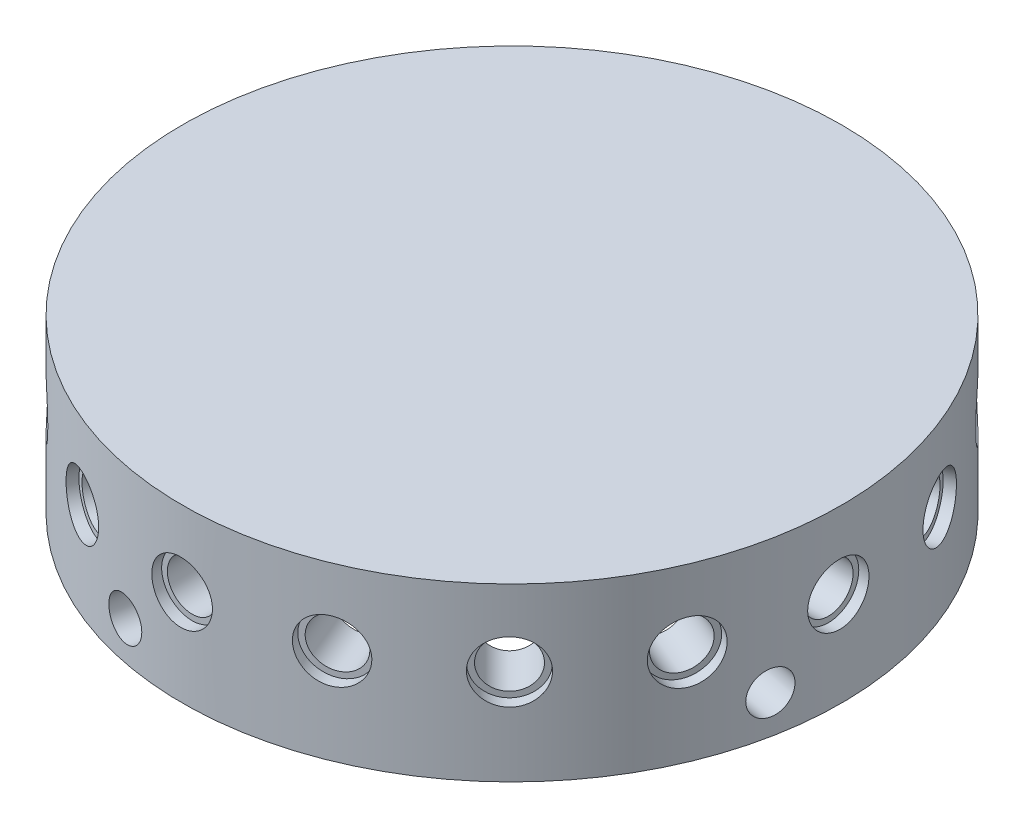
SolidWorks part; units mm, degrees
ref_plane "Płaszczyzna przednia" through (0, 0, 0) normal (0, 0, 1) x (1, 0, 0)
ref_plane "Płaszczyzna górna" through (0, 0, 0) normal (0, 1, 0) x (1, 0, 0)
ref_plane "Płaszczyzna prawa" through (0, 0, 0) normal (1, 0, 0) x (0, 0, -1)
sketch "Szkic1" plane through (0, 0, 0) normal (0, 0, 1) x (1, 0, 0)
  line L0 (0, -200.6294) -> (0, 200.6294) construction
  line L1 (0, 70.8485) -> (-86.5, 70.8485)
  line L2 (-86.5, 70.8485) -> (-86.5, 40.8485)
  line L4 (-86.5, 40.8485) -> (-86.5, 25.8485)
  line L5 (-86.5, 25.8485) -> (-70.5, 25.8485)
  line L6 (-70.5, 25.8485) -> (-70.5, 65.8485)
  line L7 (-70.5, 65.8485) -> (0, 65.8485)
  line L8 (0, 65.8485) -> (0, 70.8485)
  dimension "D1" = 70.5
  dimension "D2" = 40
  dimension "D3" = 5
  dimension "D5" = 16
revolve "Obrót1" add sketch "Szkic1" angle 360 about L0
ref_plane "Płaszczyzna1" through (86.5, 0, 0) normal (1, 0, 0) x (0, 0, -1)
sketch "Szkic2" plane through (86.5, 0, 0) normal (1, 0, 0) x (0, 0, -1)
  line L0 (86.5, 70.8485) -> (-86.5, 70.8485) construction
  circle A0 centre (-0.4671, 50.8485) radius 8
  circle A1 centre (-0.4671, 50.8485) radius 6.5
  dimension "D1" = 20
  dimension "D2" = 16
  dimension "D3" = 13
extrude "Wytnij-wyciągnięcie2" cut sketch "Szkic2" against normal blind 3
sketch "Szkic3" plane through (86.5, 0, 0) normal (1, 0, 0) x (0, 0, -1)
  circle A0 centre (-0.4671, 50.8485) radius 6.5
  circle A1 centre (-0.4671, 50.8485) radius 6.5 construction
extrude "Wytnij-wyciągnięcie3" cut sketch "Szkic3" against normal blind 30
pattern_circular "Szyk kołowy1" count 16 over 360 of "Wytnij-wyciągnięcie2", "Wytnij-wyciągnięcie3"
sketch "Szkic4" plane through (86.5, 0, 0) normal (1, 0, 0) x (0, 0, -1)
  line L0 (-86.5, 25.8485) -> (86.5, 25.8485) construction
  circle A0 centre (-0.4671, 35.8485) radius 5.5
  dimension "D1" = 10
ref_plane "Płaszczyzna3" through (-16.8753, 0, 84.8379) normal (-0.1951, 0, 0.9808) x (0, -1, 0)
sketch "Szkic6" plane through (-16.8753, 0, 84.8379) normal (-0.1951, 0, 0.9808) x (0, -1, 0)
  line L0 (-25.8485, -86.5) -> (-25.8485, 86.5) construction
  circle A0 centre (-35.8485, 0) radius 5.5
  point P2 (0, 0)
  dimension "D1" = 10
extrude "Wytnij-wyciągnięcie4" cut sketch "Szkic6" against normal up to next
pattern_circular "Szyk kołowy2" count 4 over 360 about axis through (0, -200.6294, 0) along (0, -1, 0) of "Wytnij-wyciągnięcie4" reverse direction yes
